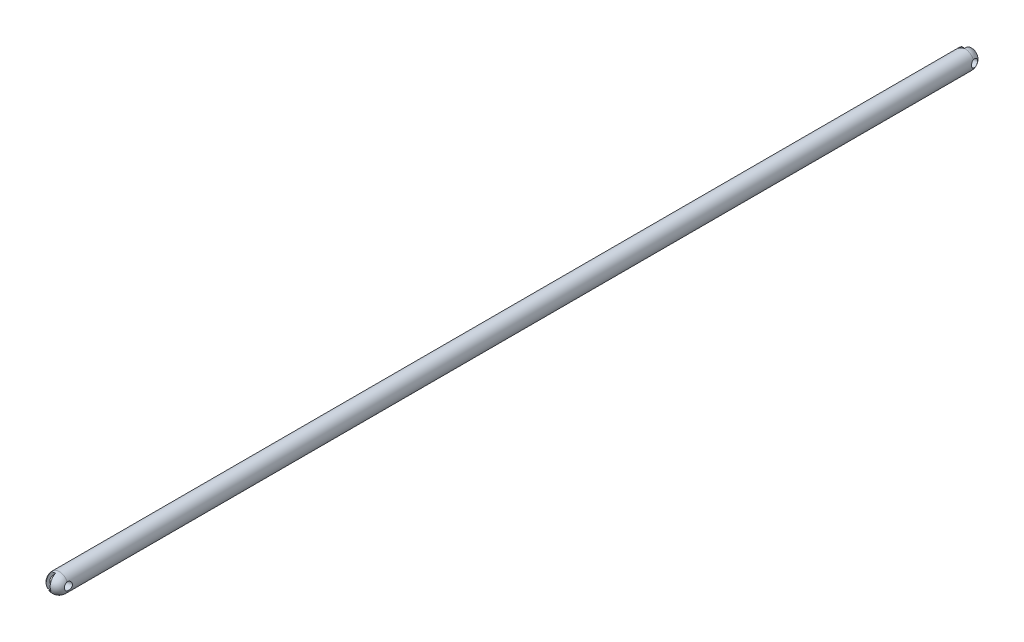
SolidWorks part; units mm, degrees
material "1060 Alloy"
ref_plane "Front Plane" through (0, 0, 0) normal (0, 0, 1) x (1, 0, 0)
ref_plane "Top Plane" through (0, 0, 0) normal (0, 1, 0) x (1, 0, 0)
ref_plane "Right Plane" through (0, 0, 0) normal (1, 0, 0) x (0, 0, -1)
sketch "Sketch1" plane through (0, 0, 0) normal (0, 0, 1) x (1, 0, 0)
  circle A0 centre (0, 0) radius 5
  dimension "D1" = 10
sketch "Sketch3" plane through (0, 0, 0) normal (1, 0, 0) x (0, 0, -1)
  line L0 (0, 0) -> (487.4056, 0)
  line L1 (0, 5) -> (0, -5) construction
  line L2 (487.4056, 0) -> (0, 0) construction
sweep "Sweep1" add profiles "Sketch1" path "Sketch3"
dome "Dome1" faces to dome 1 distance 5 reverse direction no elliptical dome no face at (5, 0, 0) parameters "D1"=5
ref_plane "Plane1" through (0, 0, -487.4056) normal (0, 0, -1) x (-1, 0, 0)
dome "Dome2" faces to dome 1 distance 5 reverse direction no elliptical dome no face at (5, 0, -487.4056) parameters "D1"=5
sketch "Sketch5" plane through (-26.5718, 229.276, -160.2731) normal (-0.0946, 0.8159, -0.5704) x (0.9955, 0.0787, -0.0524)
  line L0 (22.8435, 396.2753) -> (22.1234, 404.243)
  line L1 (22.1962, 403.4367) -> (22.5734, 399.2633) construction
  line L2 (22.1234, 404.243) -> (25.1112, 404.513)
  line L3 (25.1112, 404.513) -> (25.8313, 396.5454)
  line L4 (25.8313, 396.5454) -> (22.8435, 396.2753)
  line L5 (25.5612, 399.5333) -> (22.5734, 399.2633) construction
  line L6 (22.8434, 396.2753) -> (25.8313, 396.5454) construction
  line L7 (25.1841, 403.7068) -> (25.5612, 399.5333) construction
  arc A3 (21.2622, 404.3448) -> (25.9401, 404.7676) centre (22.2221, 419.8151) ccw construction
  point P4 (0, 0)
  point P6 (14.274, 420.4969)
  point P10 (0, 0)
  point P11 (14.4441, 421.6492)
  point P12 (9.4096, 427.7264)
  point P13 (15.9155, 418.3844)
  point P14 (9.5907, 427.5467)
extrude "Cut-Extrude2" cut sketch "Sketch5" against normal through all both and the other way through all
sketch "Sketch6" plane through (60.9078, 1.6485, -7.7397) normal (-0.9917, -0.0268, 0.126) x (0.1263, -0.0091, 0.992)
  circle A0 centre (-483.4823, -6.0549) radius 2
  circle A1 centre (-483.4823, -6.0549) radius 2 construction
extrude "Cut-Extrude3" cut sketch "Sketch6" against normal through all both and the other way through all
sketch "Sketch7" plane through (-0.0527, 1.7144, 2.4613) normal (-0.0176, 0.5715, 0.8204) x (0.9998, 0.0108, 0.0139)
  line L0 (-2.9868, -0.2808) -> (-2.5945, -4.4529) construction
  line L1 (-2.5945, -4.4529) -> (0.3923, -4.1721)
  line L2 (-2.5945, -4.4529) -> (-3.2677, 2.706)
  line L3 (-3.2677, 2.706) -> (-0.2808, 2.9868)
  line L4 (0.3923, -4.1721) -> (-0.2808, 2.9868)
  line L6 (0.3923, -4.1721) -> (0, 0) construction
  arc A0 (-3.3468, -5.5165) -> (-2.5945, -4.4529) centre (-3.5902, -4.5465) ccw construction
extrude "Cut-Extrude5" cut sketch "Sketch7" against normal through all both and the other way through all
sketch "Sketch8" plane through (0, 0, 0) normal (-0.9954, -0.0876, 0.0397) x (0.0398, 0.0011, 0.9992)
  circle A0 centre (0, 0) radius 2
  circle A1 centre (0, 0) radius 2 construction
extrude "Cut-Extrude6" cut sketch "Sketch8" against normal through all both and the other way through all
